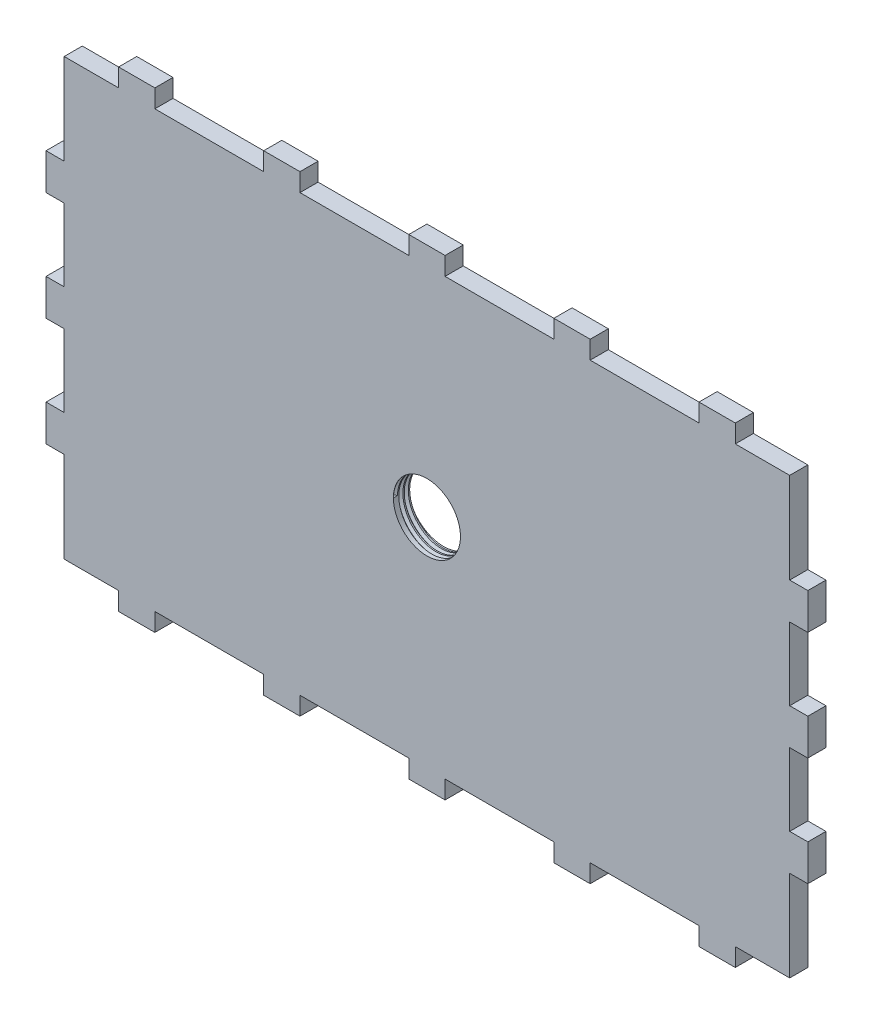
SolidWorks part; units mm, degrees
ref_plane "Ön Düzlem" through (0, 0, 0) normal (0, 0, 1) x (1, 0, 0)
ref_plane "Üst Düzlem" through (0, 0, 0) normal (0, 1, 0) x (1, 0, 0)
ref_plane "Sağ Düzlem" through (0, 0, 0) normal (1, 0, 0) x (0, 0, -1)
sketch "Sketch1" plane through (0, 0, 0) normal (0, 0, 1) x (1, 0, 0)
  line L0 (-85, 60) -> (-85, 65)
  line L1 (-100, -60) -> (-85, -60)
  line L2 (-100, -60) -> (-100, -35)
  line L3 (-100, 60) -> (-85, 60)
  line L4 (100, -60) -> (100, -35)
  line L5 (-100, -60) -> (100, 60) construction
  line L6 (-100, 60) -> (100, -60) construction
  line L7 (-85, 65) -> (-75, 65)
  line L8 (-75, 65) -> (-75, 60)
  line L9 (-45, 60) -> (-45, 65)
  line L10 (-35, 65) -> (-35, 60)
  line L11 (-45, 65) -> (-35, 65)
  line L12 (-5, 60) -> (-5, 65)
  line L13 (5, 65) -> (5, 60)
  line L14 (-5, 65) -> (5, 65)
  line L15 (35, 60) -> (35, 65)
  line L16 (45, 65) -> (45, 60)
  line L17 (35, 65) -> (45, 65)
  line L18 (75, 60) -> (75, 65)
  line L19 (85, 65) -> (85, 60)
  line L20 (75, 65) -> (85, 65)
  line L21 (-75, 60) -> (-45, 60)
  line L22 (-35, 60) -> (-5, 60)
  line L23 (5, 60) -> (35, 60)
  line L24 (45, 60) -> (75, 60)
  line L25 (85, 60) -> (100, 60)
  line L26 (-105, 0) -> (105, 0) construction
  line L27 (0, -60) -> (0, 60) construction
  line L28 (-100, 35) -> (-105, 35)
  line L29 (-105, 35) -> (-105, 25)
  line L30 (-105, 25) -> (-100, 25)
  line L31 (-105, -5) -> (-100, -5)
  line L32 (-100, 5) -> (-105, 5)
  line L33 (-105, 5) -> (-105, -5)
  line L34 (-105, -35) -> (-100, -35)
  line L35 (-100, -25) -> (-105, -25)
  line L36 (-105, -25) -> (-105, -35)
  line L37 (105, 25) -> (100, 25)
  line L38 (100, 35) -> (105, 35)
  line L39 (105, 35) -> (105, 25)
  line L40 (100, 5) -> (105, 5)
  line L41 (105, 5) -> (105, -5)
  line L42 (105, -5) -> (100, -5)
  line L43 (100, -25) -> (105, -25)
  line L44 (105, -25) -> (105, -35)
  line L45 (105, -35) -> (100, -35)
  line L46 (85, -65) -> (85, -60)
  line L47 (75, -65) -> (85, -65)
  line L48 (75, -60) -> (75, -65)
  line L49 (45, -65) -> (45, -60)
  line L50 (35, -65) -> (45, -65)
  line L51 (35, -60) -> (35, -65)
  line L52 (5, -65) -> (5, -60)
  line L53 (-5, -65) -> (5, -65)
  line L55 (-35, -65) -> (-35, -60)
  line L56 (-45, -65) -> (-35, -65)
  line L57 (-45, -60) -> (-45, -65)
  line L58 (-75, -65) -> (-75, -60)
  line L59 (-85, -65) -> (-75, -65)
  line L60 (-85, -60) -> (-85, -65)
  line L61 (-75, -60) -> (-45, -60)
  line L63 (5, -60) -> (35, -60)
  line L64 (45, -60) -> (75, -60)
  line L65 (85, -60) -> (100, -60)
  line L66 (-100, -25) -> (-100, -5)
  line L67 (-100, 5) -> (-100, 25)
  line L68 (-100, 35) -> (-100, 60)
  line L69 (100, 35) -> (100, 60)
  line L70 (100, 5) -> (100, 25)
  line L71 (100, -25) -> (100, -5)
  line L72 (-35, -60) -> (-5, -60)
  line L73 (-5, -60) -> (-5, -65)
  circle A4 centre (0, 0) radius 9.25
  point P0 (0, 0)
  dimension "D3" = 18.5
  dimension "D1" = 120
  dimension "D2" = 200
  dimension "D7" = 10
  dimension "D8" = 5
  dimension "D9" = 15
  dimension "D11" = 30
  dimension "D12" = 5
  dimension "D13" = 10
  dimension "D14" = 25
  dimension "D16" = 30
  dimension "D17" = 20
  dimension "D18" = 30
  dimension "D10" = 5
  dimension "D15" = 3
extrude "Boss-Extrude1" add sketch "Sketch1" along normal blind 5
thread "Thread1" pitch 1.5 method cut profile "Thread Profile1" start angle 0, offset 0, length 0, pitch 1.5, diameter 18.5
ref_plane "Plane1" through (-9.25, 0, 5) normal (0, -1, 0) x (-1, 0, 0)
sketch "Thread Profile1" plane through (-9.25, 0, 5) normal (0, -1, 0) x (-1, 0, 0)
  line L0 (0, 0) -> (0, 1.5) construction
  line L1 (0, 0) -> (0.8119, 0.4687)
  line L2 (0.8119, 0.4687) -> (0.8119, 0.6562)
  line L3 (0.8119, 0.6562) -> (0, 1.125)
  line L4 (0.8119, 0.5625) -> (0, 0.5625) construction
  line L11 (0, 0) -> (0, 1.125)
  point P2 (0, 0)
  dimension "Pitch" = 1.5
  dimension "Profile_Angle" = 60
  dimension "Profile_Land" = 0.1875
  dimension "Profile_Height" = 0.8119
